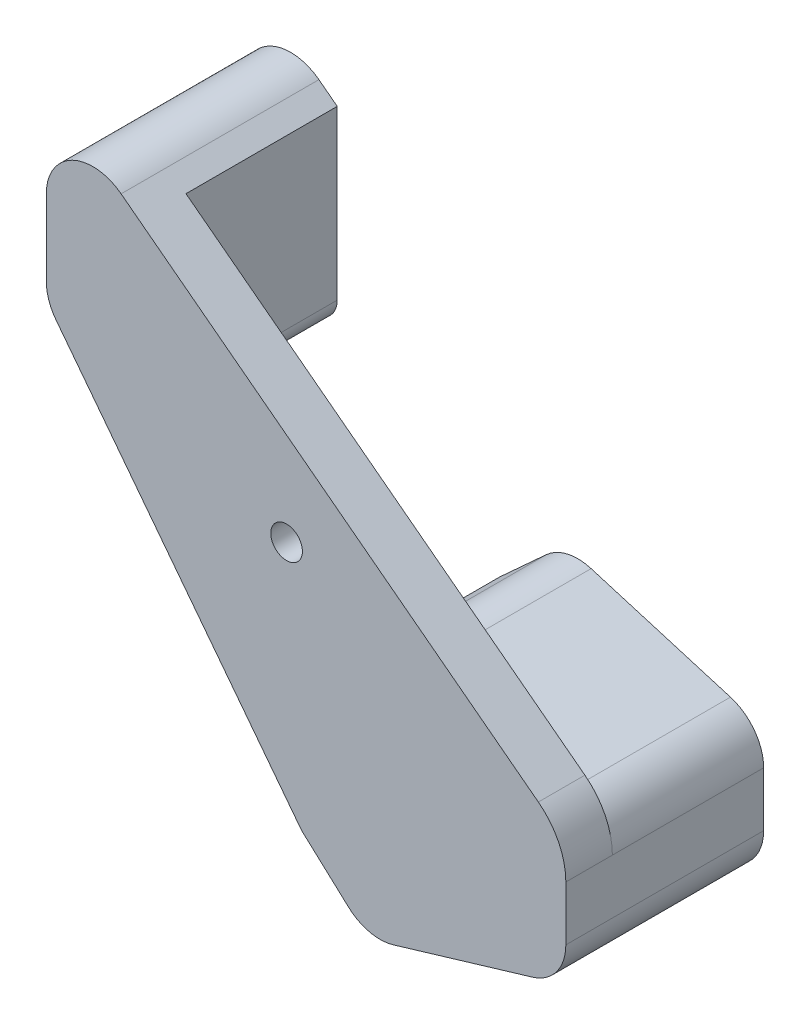
SolidWorks part; units mm, degrees
ref_plane "Front Plane" through (0, 0, 0) normal (0, 0, 1) x (1, 0, 0)
ref_plane "Top Plane" through (0, 0, 0) normal (0, 1, 0) x (1, 0, 0)
ref_plane "Right Plane" through (0, 0, 0) normal (1, 0, 0) x (0, 0, -1)
sketch "Sketch1" plane through (0, 0, 0) normal (0, 0, 1) x (1, 0, 0)
  line L0 (0, 0) -> (0, 12.7)
  line L1 (0, 12.7) -> (11.1125, 22.86)
  line L3 (11.1125, 22.86) -> (38.1, 14.7942)
  line L4 (38.1, 14.7942) -> (38.1, -19.05)
  line L5 (11.1125, 12.7) -> (11.1125, 0) construction
  line L6 (11.1125, 6.35) -> (30.1625, 6.35) construction
  line L7 (11.1125, -10.16) -> (38.1, -2.0942)
  line L8 (0, 0) -> (11.1125, -10.16)
  circle A0 centre (11.1125, 12.7) radius 2.032
  circle A1 centre (11.1125, 0) radius 2.032
  circle A2 centre (30.1625, 6.35) radius 2.032
  dimension "D3" = 4.064
  dimension "D1" = 73.36
  dimension "D2" = 38.1
  dimension "D4" = 11.1125
  dimension "D5" = 12.7
  dimension "D6" = 10.16
  dimension "D7" = 19.05
  dimension "D8" = 19.05
extrude "Boss-Extrude1" add sketch "Sketch1" along normal blind 20.6375 contours L0 L8 L7 L4 L3 L1 A2 A1 A0 region at (18.6064, 6.35, 0)
fillet "Fillet1" radius 6.35 6 edges at (38.1, 14.7942, 10.3187) (11.1125, 22.86, 10.3187) (0, 12.7, 10.3187) (38.1, -2.0942, 10.3187) (11.1125, -10.16, 10.3187) (0, 0, 10.3187)
sketch "Sketch3" plane through (0, 0, 20.6375) normal (0, 0, 1) x (1, 0, 0)
  line L0 (2.0652, -1.8882) -> (-32.7759, 43.4132)
  line L1 (-32.7759, 43.4132) -> (-32.7759, 68.8132)
  line L2 (-32.7759, 68.8132) -> (34.3497, 17.6393)
  line L6 (14.5601, -9.1296) -> (33.5684, -3.4485)
  line L7 (38.1, 2.6355) -> (38.1, 10.0645)
  line L8 (33.5684, 16.1485) -> (14.5601, 21.8296)
  line L9 (8.4569, 20.432) -> (2.0652, 14.5882)
  line L10 (0, 9.9017) -> (0, 2.7983)
  line L11 (2.0652, -1.8882) -> (8.4569, -7.732)
  line L12 (14.5601, -9.1296) -> (33.5684, -3.4485)
  line L13 (38.1, 2.6355) -> (38.1, 10.0645)
  line L17 (2.0652, -1.8882) -> (8.4569, -7.732)
  arc A0 (38.1, 10.0645) -> (34.3497, 17.6393) centre (28.575, 10.0645) ccw
  circle A1 centre (0, 31.1519) radius 2.159 construction
  circle A2 centre (0, 31.1519) radius 2.159
  arc A6 (33.5684, -3.4485) -> (38.1, 2.6355) centre (31.75, 2.6355) ccw
  arc A7 (38.1, 10.0645) -> (33.5684, 16.1485) centre (31.75, 10.0645) ccw
  arc A8 (14.5601, 21.8296) -> (8.4569, 20.432) centre (12.7417, 15.7455) ccw
  arc A9 (2.0652, 14.5882) -> (0, 9.9017) centre (6.35, 9.9017) ccw
  arc A10 (0, 2.7983) -> (2.0652, -1.8882) centre (6.35, 2.7983) ccw
  arc A11 (8.4569, -7.732) -> (14.5601, -9.1296) centre (12.7417, -3.0455) ccw
  arc A12 (33.5684, -3.4485) -> (38.1, 2.6355) centre (31.75, 2.6355) ccw
  arc A17 (8.4569, -7.732) -> (14.5601, -9.1296) centre (12.7417, -3.0455) ccw
  dimension "D2" = 57.15
  dimension "D3" = 9.525
  dimension "D4" = 170
  dimension "D5" = 25.4
  dimension "D1" = 0
extrude "Boss-Extrude2" add sketch "Sketch3" along normal blind 6.35
fillet "Fillet2" radius 6.35 2 edges at (-32.7759, 43.4132, 23.8125) (-32.7759, 68.8132, 23.8125)
sketch "Sketch4" plane through (0, 0, 20.6375) normal (0, 0, -1) x (-1, 0, 0)
  line L0 (32.7759, 55.9874) -> (32.7759, 45.5727) construction
  line L1 (32.7759, 55.9874) -> (32.7759, 45.5727)
  line L2 (22.5761, 61.0373) -> (20.0759, 59.1312)
  line L3 (-34.3497, 17.6393) -> (22.5761, 61.0373) construction
  line L4 (31.4594, 41.7014) -> (20.0759, 26.9003)
  line L5 (20.0759, 59.1312) -> (20.0759, 26.9003)
  arc A0 (31.4594, 41.7014) -> (32.7759, 45.5727) centre (26.4259, 45.5727) ccw construction
  arc A1 (32.7759, 55.9874) -> (22.5761, 61.0373) centre (26.4259, 55.9874) ccw construction
  arc A2 (31.4594, 41.7014) -> (32.7759, 45.5727) centre (26.4259, 45.5727) ccw
  arc A3 (32.7759, 55.9874) -> (22.5761, 61.0373) centre (26.4259, 55.9874) ccw
  circle A4 centre (26.4259, 55.9874) radius 2.032
  circle A5 centre (26.4259, 45.5727) radius 2.032
  dimension "D2" = 4.064
  dimension "D1" = 12.7
extrude "Boss-Extrude3" add sketch "Sketch4" along normal up to surface (20.6375 mm away)
ref_plane "Plane1" through (0, 0, -2.54) normal (0, 0, -1) x (-1, 0, 0)
fillet "Fillet3" radius 3.175 1 edges at (-20.0759, 26.9003, 10.3187)
mirror "Mirror2" [suppressed] about plane through (0, 0, -2.54) normal (0, 0, -1) of bodies 103
delete or keep bodies "Body-Delete/Keep 1" [suppressed] type delete bodies bodies 103
